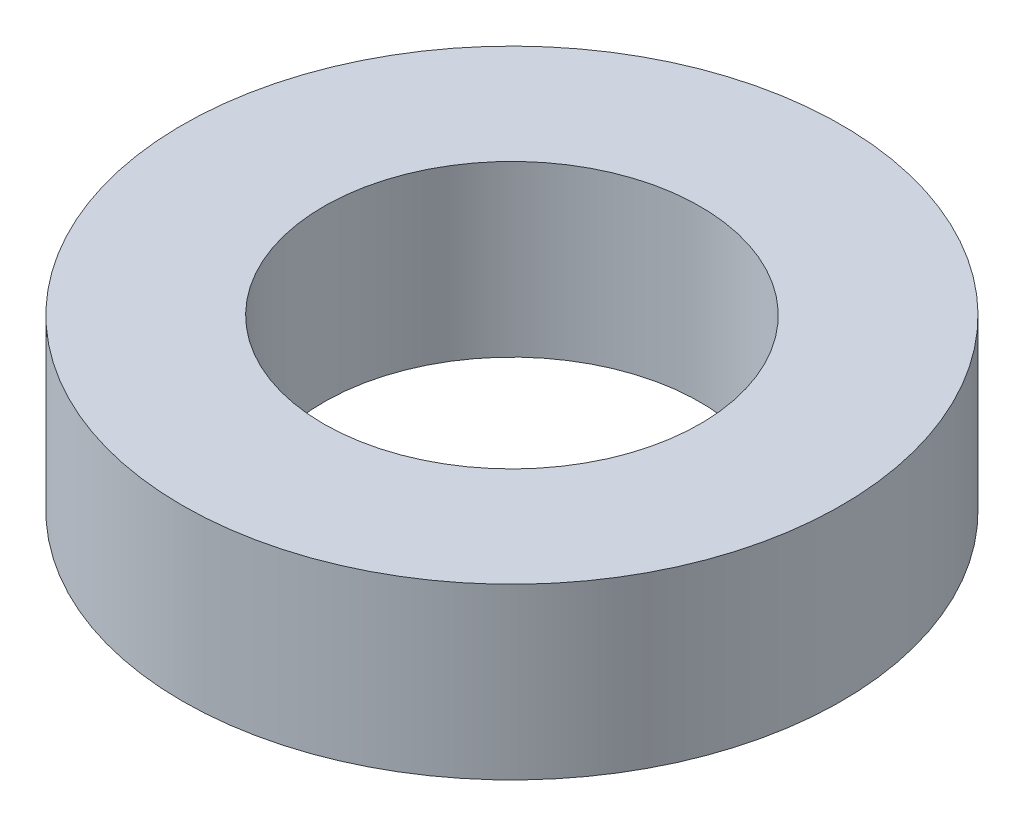
SolidWorks part; units mm, degrees
ref_plane "Front Plane" through (0, 0, 0) normal (0, 0, 1) x (1, 0, 0)
ref_plane "Top Plane" through (0, 0, 0) normal (0, 1, 0) x (1, 0, 0)
ref_plane "Right Plane" through (0, 0, 0) normal (1, 0, 0) x (0, 0, -1)
sketch "Sketch1" plane through (0, 0, 0) normal (0, 1, 0) x (1, 0, 0)
  circle A0 centre (0, 0) radius 35
  dimension "FLANGE_OD" = 70
extrude "Boss-Extrude1" add sketch "Sketch1" along normal blind 18
sketch "Sketch2" plane through (0, 0, 0) normal (0, 1, 0) x (1, 0, 0)
  circle A0 centre (0, 0) radius 20
  dimension "BORE_D" = 40
extrude "Cut-Extrude1" cut sketch "Sketch2" along normal through all
sketch "Sketch3" plane through (0, 18, 0) normal (0, 1, 0) x (1, 0, 0)
  circle A0 centre (0, 0) radius 13.6474 construction
  circle A1 centre (-13.6474, 0) radius 2.543
  dimension "BOLT_D" = 5.0859
  dimension "BOLT_PCD" = 27.2949
extrude "Cut-Extrude2" cut sketch "Sketch3" against normal blind 16.5014 rebuild error yes
pattern_circular "CirPattern1" count 8 over 360 rebuild error yes
